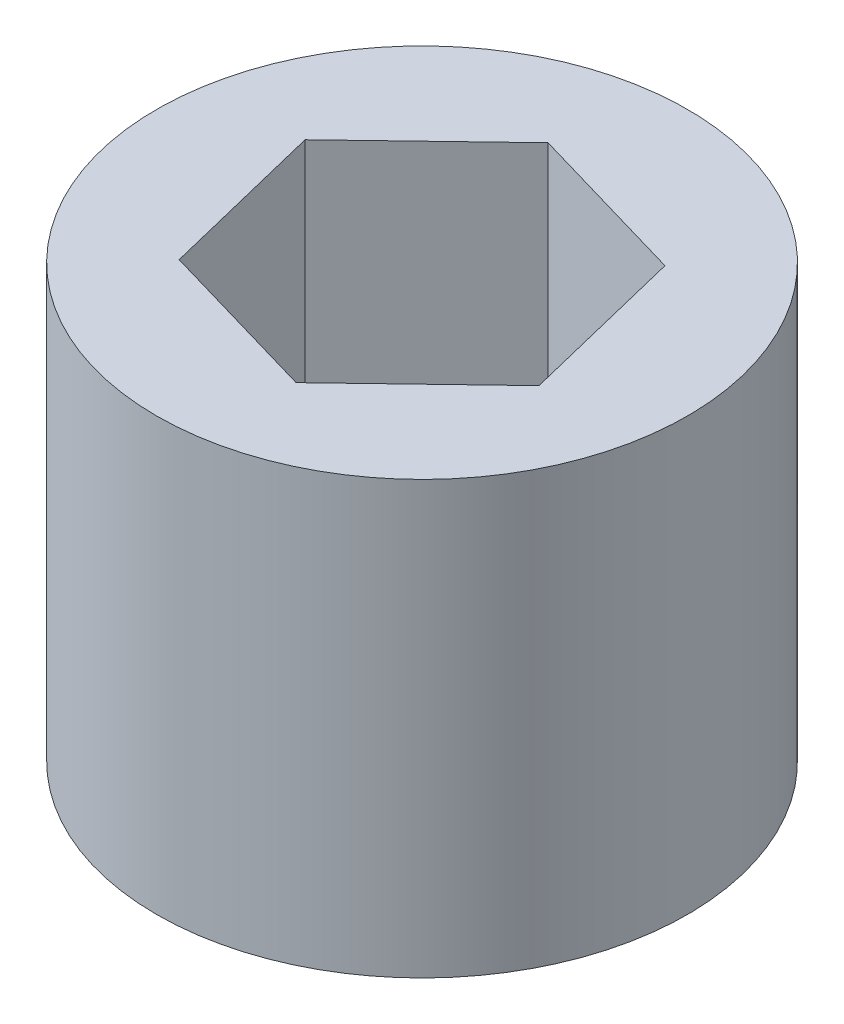
SolidWorks part; units mm, degrees
ref_plane "Front" through (0, 0, 0) normal (0, 0, 1) x (1, 0, 0)
ref_plane "Top" through (0, 0, 0) normal (0, 1, 0) x (1, 0, 0)
ref_plane "Right" through (0, 0, 0) normal (1, 0, 0) x (0, 0, -1)
sketch "Sketch1" plane through (0, 0, 0) normal (0, 1, 0) x (1, 0, 0)
  circle A0 centre (0, 0) radius 4.55
extrude "Boss-Extrude1" add sketch "Sketch1" along normal blind 7.4
sketch "Sketch2" plane through (0, 7.4, 0) normal (0, 1, 0) x (1, 0, 0)
  line L1 (-2.1264, -2.0368) -> (0.7008, -2.8599)
  line L2 (0.7008, -2.8599) -> (2.8271, -0.8231)
  line L3 (2.8271, -0.8231) -> (2.1264, 2.0368)
  line L4 (2.1264, 2.0368) -> (-0.7008, 2.8599)
  line L5 (-0.7008, 2.8599) -> (-2.8271, 0.8231)
  line L6 (-2.8271, 0.8231) -> (-2.1264, -2.0368)
  circle A0 centre (0, 0) radius 2.55 construction
  dimension "D1" = 5.1
extrude "Cut-Extrude1" cut sketch "Sketch2" against normal blind 15
